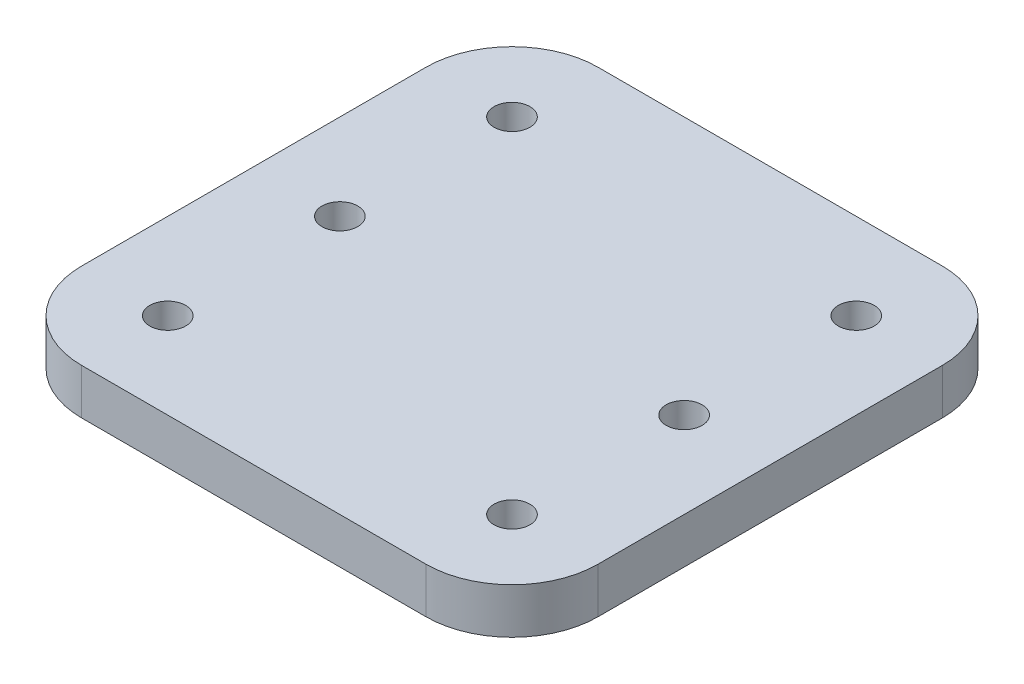
SolidWorks part; units mm, degrees
ref_plane "Front Plane" through (0, 0, 0) normal (0, 0, 1) x (1, 0, 0)
ref_plane "Top Plane" through (0, 0, 0) normal (0, 1, 0) x (1, 0, 0)
ref_plane "Right Plane" through (0, 0, 0) normal (1, 0, 0) x (0, 0, -1)
sketch "Sketch1" plane through (0, 0, 0) normal (0, 1, 0) x (1, 0, 0)
  line L1 (-24, -36) -> (24, -36)
  line L2 (-36, -24) -> (-36, 24)
  line L3 (-24, 36) -> (24, 36)
  line L4 (36, -24) -> (36, 24)
  line L5 (-36, -36) -> (36, 36) construction
  line L6 (-36, 36) -> (36, -36) construction
  arc A0 (24, 36) -> (36, 24) centre (24, 24) cw
  arc A1 (24, -36) -> (36, -24) centre (24, -24) ccw
  arc A2 (-24, -36) -> (-36, -24) centre (-24, -24) cw
  arc A3 (-36, 24) -> (-24, 36) centre (-24, 24) cw
  point P0 (0, 0)
  dimension "D1" = 12
  dimension "D2" = 72
  dimension "D3" = 72
extrude "Boss-Extrude1" add sketch "Sketch1" along normal blind 6.35
sketch "Sketch2" plane through (0, 6.35, 0) normal (0, 1, 0) x (1, 0, 0)
  line L0 (-36, 0) -> (36, 0) construction
  line L1 (-36, 24) -> (-36, -24) construction
  line L2 (36, -24) -> (36, 24) construction
  line L3 (-36, 12) -> (36, 12) construction
  circle A0 centre (-24, 24) radius 12 construction
  circle A1 centre (-24, 24) radius 2.5
  arc A2 (-24, 36) -> (-36, 24) centre (-24, 24) ccw construction
  circle A3 centre (24, 24) radius 2.5
  circle A4 centre (24, -24) radius 2.5
  circle A5 centre (-24, -24) radius 2.5
  point P11 (38, 24)
  point P20 (38, -24)
  dimension "D3" = 5
  dimension "D1" = 24
  dimension "D2" = 2
  dimension "D4" = 2
extrude "Cut-Extrude1" cut sketch "Sketch2" against normal through all
sketch "Sketch3" plane through (0, 6.35, 0) normal (0, 1, 0) x (1, 0, 0)
  line L0 (-24, 0) -> (24, 0) construction
  line L1 (-24, 24) -> (-24, -24) construction
  line L2 (24, 24) -> (24, -24) construction
  circle A1 centre (-24, 0) radius 2.5
  circle A3 centre (24, 0) radius 2.5
  dimension "D1" = 5
extrude "Cut-Extrude2" cut sketch "Sketch3" against normal through all
